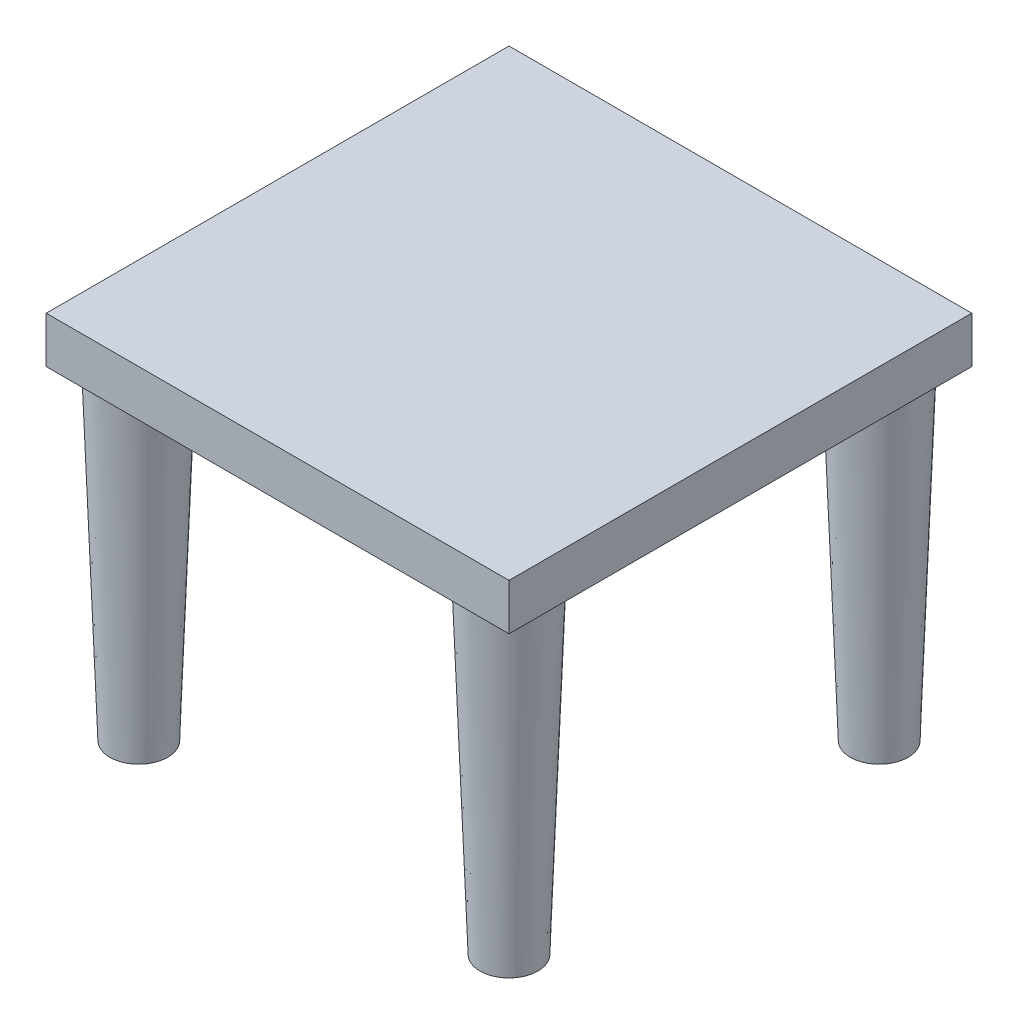
SolidWorks part; units mm, degrees
ref_plane "Front Plane" through (0, 0, 0) normal (0, 0, 1) x (1, 0, 0)
ref_plane "Top Plane" through (0, 0, 0) normal (0, 1, 0) x (1, 0, 0)
ref_plane "Right Plane" through (0, 0, 0) normal (1, 0, 0) x (0, 0, -1)
sketch "Sketch1" plane through (0, 0, 0) normal (0, 1, 0) x (1, 0, 0)
  line L1 (-50, 50) -> (50, 50)
  line L2 (-50, 50) -> (-50, -50)
  line L3 (-50, -50) -> (50, -50)
  line L4 (50, 50) -> (50, -50)
  line L5 (-50, 50) -> (50, -50) construction
  line L6 (-50, -50) -> (50, 50) construction
  point P0 (0, 0)
  dimension "D1" = 100
extrude "Boss-Extrude1" add sketch "Sketch1" along normal mid plane 10
ref_plane "Plane1" through (0, -75, 0) normal (0, 1, 0) x (1, 0, 0)
sketch "Sketch2" plane through (0, -5, 0) normal (0, -1, 0) x (1, 0, 0)
  line L0 (-50, -50) -> (-50, 50) construction
  line L1 (50, -50) -> (-50, -50) construction
  line L2 (50, 50) -> (50, -50) construction
  line L3 (-50, 50) -> (50, 50) construction
  circle A0 centre (-40, 40) radius 8.75
  circle A1 centre (40, 40) radius 8.75
  circle A2 centre (40, -40) radius 8.75
  circle A3 centre (-40, -40) radius 8.75
  dimension "D1" = 17.5
  dimension "D2" = 10
  dimension "D3" = 10
  dimension "D4" = 10
  dimension "D5" = 10
  dimension "D6" = 10
  dimension "D7" = 10
  dimension "D8" = 10
  dimension "D9" = 10
sketch "Sketch3" plane through (0, -75, 0) normal (0, 1, 0) x (1, 0, 0)
  circle A0 centre (-40, -40) radius 6.25
  circle A1 centre (-40, 40) radius 6.25
  circle A2 centre (40, 40) radius 6.25
  circle A3 centre (40, -40) radius 6.25
  dimension "D1" = 12.5
loft "Loft1" add section "Sketch2" section "Sketch3" connector at (-44.3687, -5, -32.4186) connector at (-41.9052, -75, -34.0475)
loft "Loft2" add section "Sketch2<4>" section "Sketch3<3>" connector at (-31.252, -5, 40.1869) connector at (-33.7823, -75, 40.6343)
sketch "Sketch2<4>" plane through (0, -5, 0) normal (0, -1, 0) x (1, 0, 0) same geometry as "Sketch2"
sketch "Sketch3<3>" plane through (0, -75, 0) normal (0, 1, 0) x (1, 0, 0) same geometry as "Sketch3"
loft "Loft3" add section "Sketch2<5>" section "Sketch3<4>" connector at (38.5878, -5, 31.3647) connector at (39.5527, -75, 33.766)
sketch "Sketch2<5>" plane through (0, -5, 0) normal (0, -1, 0) x (1, 0, 0) same geometry as "Sketch2"
sketch "Sketch3<4>" plane through (0, -75, 0) normal (0, 1, 0) x (1, 0, 0) same geometry as "Sketch3"
loft "Loft4" add section "Sketch2<6>" section "Sketch3<5>" connector at (43.7405, -5, -32.0898) connector at (43.3886, -75, -34.7484)
sketch "Sketch2<6>" plane through (0, -5, 0) normal (0, -1, 0) x (1, 0, 0) same geometry as "Sketch2"
sketch "Sketch3<5>" plane through (0, -75, 0) normal (0, 1, 0) x (1, 0, 0) same geometry as "Sketch3"
